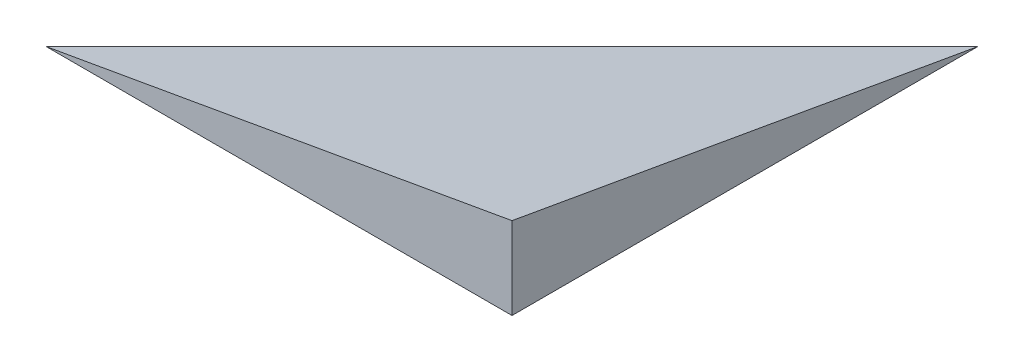
SolidWorks part; units mm, degrees
ref_plane "Front Plane" through (0, 0, 0) normal (0, 0, 1) x (1, 0, 0)
ref_plane "Top Plane" through (0, 0, 0) normal (0, 1, 0) x (1, 0, 0)
ref_plane "Right Plane" through (0, 0, 0) normal (1, 0, 0) x (0, 0, -1)
ref_axis "Axis1" through (0, 0, -88.99) along (0, 0, 1)
ref_plane "Plane1" through (0, 0, 0) normal (-0.1736, 0.9848, 0) x (0, 0, 1)
sketch "Sketch1" plane through (0, 0, 0) normal (0, 0, 1) x (1, 0, 0)
  line L0 (0, 0) -> (172.3414, 30.3884)
  line L1 (112.1373, 19.7728) -> (-112.1373, -19.7728) construction
  line L2 (172.3414, 30.3884) -> (172.3414, 0)
  line L3 (16.7136, 0) -> (-16.7136, 0) construction
  line L9 (0, 0) -> (172.3414, 0)
  dimension "D1" = 175
sketch "Sketch3" plane through (0, 0, 0) normal (0, 1, 0) x (1, 0, 0)
  line L0 (172.3414, 0) -> (172.3414, 172.3414)
  line L1 (0, 0) -> (172.3414, 0) construction
  line L2 (-55, 0) -> (55, 0) construction
  line L3 (172.3414, 172.3414) -> (0, 0)
  line L4 (0, 0) -> (172.3414, 0)
  point P6 (170.2651, 0)
  dimension "D2" = 45
loft "Loft1" add profiles "Sketch3", "Sketch1" connector at (172.3414, 0, -172.3414) connector at (172.3414, 30.3884, 0)
ref_plane "Plane2" through (0, 0, -172.3414) normal (0, 0, 1) x (1, 0, 0)
sketch "Sketch4" [suppressed] plane through (0, 0, -172.3414) normal (0, 0, 1) x (1, 0, 0)
  line L3 (-172.3414, 0) -> (-172.3414, -30.3884)
  line L7 (94.7933, 0) -> (-94.7933, 0) construction
  line L8 (-172.3414, -30.3884) -> (0, 0)
  line L9 (0, 0) -> (-172.3414, 0)
  line L13 (112.1373, 19.7728) -> (-112.1373, -19.7728) construction
  dimension "D1" = 175
sketch "Sketch5" [suppressed] plane through (0, 0, 0) normal (0, 1, 0) x (1, 0, 0)
  line L1 (-172.3414, 0) -> (-172.3414, 172.3414)
  line L2 (0, 172.3414) -> (-172.3414, 172.3414) construction
  line L3 (-172.3414, 0) -> (0, 172.3414)
  line L5 (-172.3414, 172.3414) -> (0, 172.3414) construction
  line L6 (0, -33.43) -> (0, 33.43) construction
  line L8 (-33.43, 172.3414) -> (33.43, 172.3414) construction
  line L11 (-172.3414, 172.3414) -> (0, 172.3414)
ref_axis "Axis2" through (0, -1.5249, 0) along (0, 1, 0)
